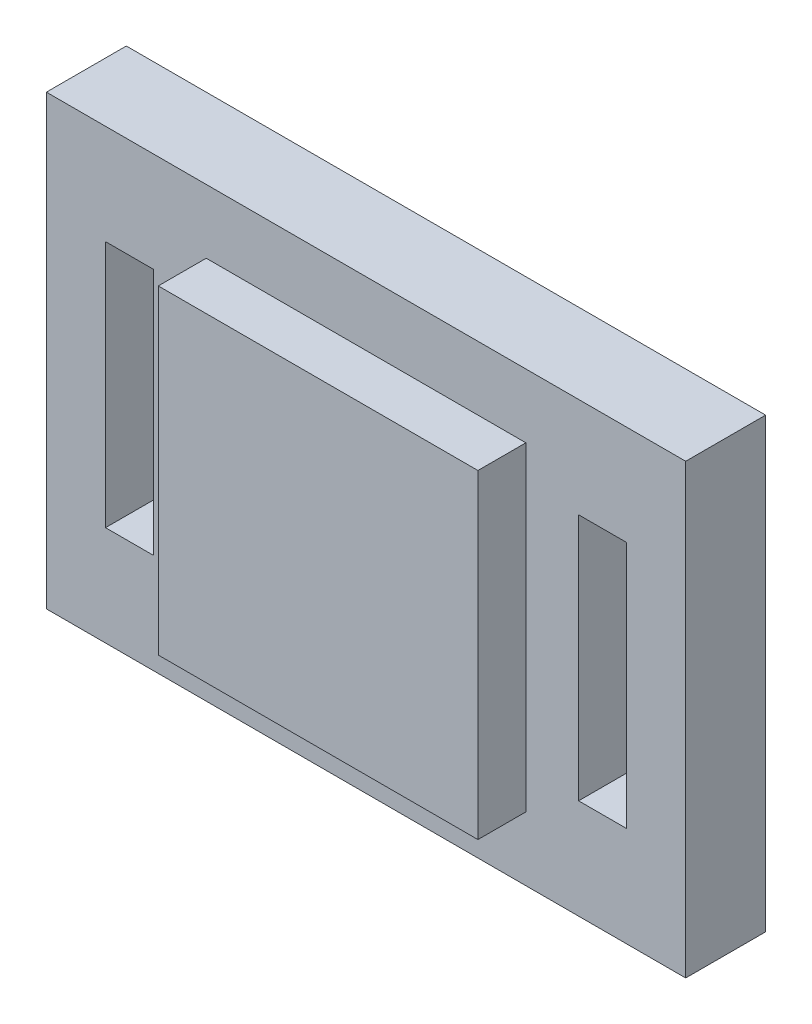
SolidWorks part; units mm, degrees
ref_plane "Alzado" through (0, 0, 0) normal (0, 0, 1) x (1, 0, 0)
ref_plane "Planta" through (0, 0, 0) normal (0, 1, 0) x (1, 0, 0)
ref_plane "Vista lateral" through (0, 0, 0) normal (1, 0, 0) x (0, 0, -1)
sketch "Croquis1" plane through (0, 0, 0) normal (0, 0, 1) x (1, 0, 0)
  line L0 (-39.1455, 0) -> (34.6181, 0) construction
  line L1 (-20, -14) -> (20, -14)
  line L2 (-20, -14) -> (-20, 14)
  line L3 (-20, 14) -> (20, 14)
  line L4 (20, -14) -> (20, 14)
  line L5 (-20, -14) -> (20, 14) construction
  line L6 (-20, 14) -> (20, -14) construction
  line L7 (0, 15.7634) -> (0, -15.7728) construction
  line L8 (13.3, -7.75) -> (16.3, -7.75)
  line L9 (13.3, -7.75) -> (13.3, 7.75)
  line L10 (13.3, 7.75) -> (16.3, 7.75)
  line L11 (16.3, -7.75) -> (16.3, 7.75)
  line L12 (13.3, -7.75) -> (16.3, 7.75) construction
  line L13 (13.3, 7.75) -> (16.3, -7.75) construction
  line L14 (-16.3, -7.75) -> (-13.3, -7.75)
  line L15 (-16.3, -7.75) -> (-16.3, 7.75)
  line L16 (-16.3, 7.75) -> (-13.3, 7.75)
  line L17 (-13.3, -7.75) -> (-13.3, 7.75)
  line L18 (-16.3, -7.75) -> (-13.3, 7.75) construction
  line L19 (-16.3, 7.75) -> (-13.3, -7.75) construction
  point P0 (0, 0)
  point P8 (14.8, 0)
  point P13 (-14.8, 0)
  dimension "D1" = 40
  dimension "D2" = 28
  dimension "D3" = 26.6
  dimension "D4" = 3
  dimension "D5" = 3
  dimension "D6" = 15.5
  dimension "D7" = 15.5
extrude "Saliente-Extruir1" add sketch "Croquis1" along normal mid plane 5
sketch "Croquis2" plane through (0, 0, 2.5) normal (0, 0, 1) x (1, 0, 0)
  line L1 (-10, -10) -> (10, -10)
  line L2 (-10, -10) -> (-10, 10)
  line L3 (-10, 10) -> (10, 10)
  line L4 (10, -10) -> (10, 10)
  line L5 (-10, -10) -> (10, 10) construction
  line L6 (-10, 10) -> (10, -10) construction
  point P0 (0, 0)
  dimension "D1" = 20
  dimension "D2" = 20
extrude "Saliente-Extruir2" add sketch "Croquis2" along normal blind 3
